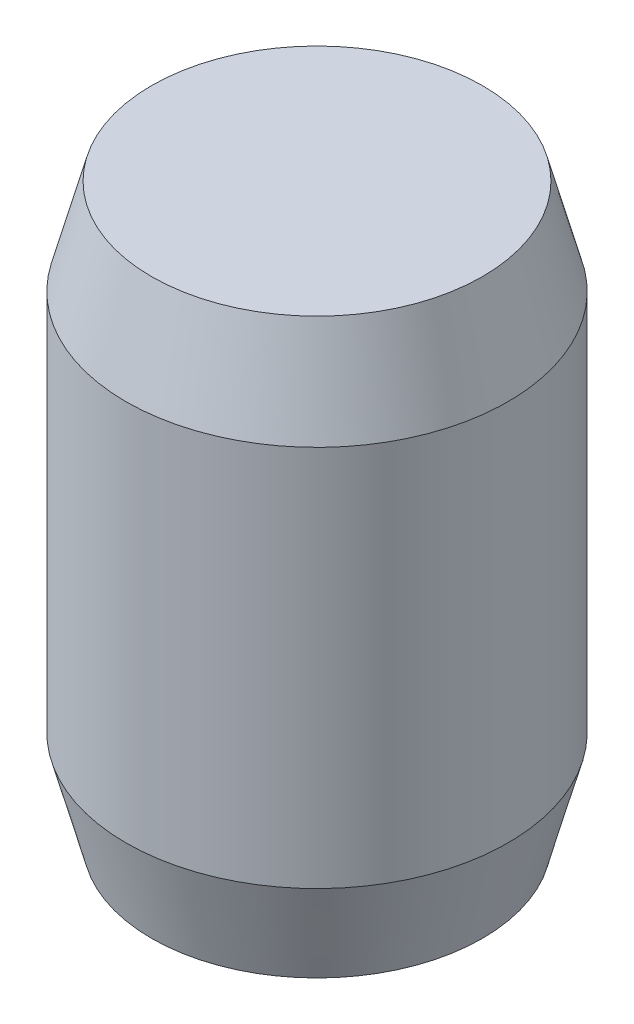
SolidWorks part; units mm, degrees
ref_plane "前视基准面" through (0, 0, 0) normal (0, 0, 1) x (1, 0, 0)
ref_plane "上视基准面" through (0, 0, 0) normal (0, 1, 0) x (1, 0, 0)
ref_plane "右视基准面" through (0, 0, 0) normal (1, 0, 0) x (0, 0, -1)
sketch "草图2" plane through (0, 0, 0) normal (0, 0, 1) x (1, 0, 0)
  line L0 (1.7321, 6) -> (2, 5)
  line L1 (0, 0) -> (1.7321, 0)
  line L2 (0, 0) -> (0, 6)
  line L3 (0, 6) -> (1.7321, 6)
  line L4 (2, 1) -> (2, 5)
  line L5 (2, 1) -> (1.7321, 0)
  dimension "D1" = 2
  dimension "D2" = 6
  dimension "D3" = 1
  dimension "D4" = 15
  dimension "D5" = 1
revolve "旋转1" add sketch "草图2" angle 360 about L2
ref_axis "基准轴1" through (0, 5, 0) along (0, -1, 0)
ref_plane "基准面1" through (0, 3, 0) normal (0, 1, 0) x (1, 0, 0)
equation "\"D5@草图2\"=\"D3@草图2\""
